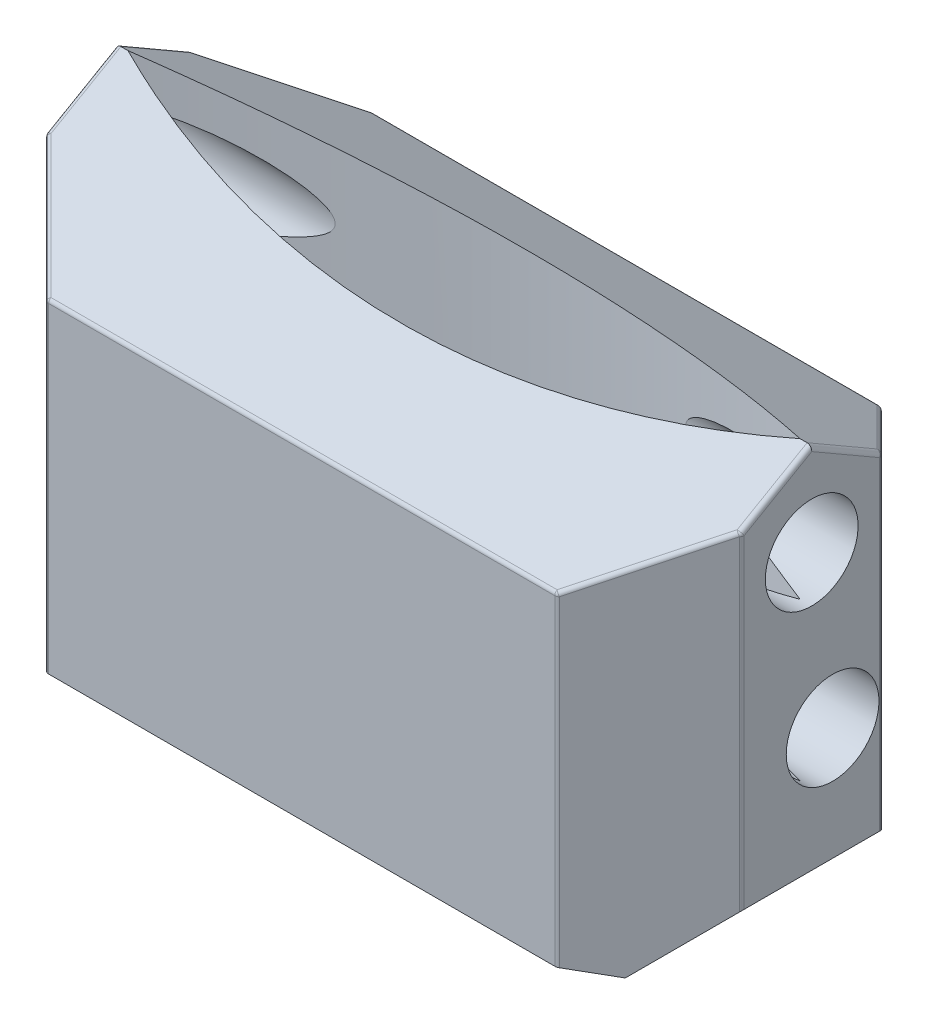
SolidWorks part; units mm, degrees
ref_plane "Front" through (0, 0, 0) normal (0, 0, 1) x (1, 0, 0)
ref_plane "Top" through (0, 0, 0) normal (0, 1, 0) x (1, 0, 0)
ref_plane "Right" through (0, 0, 0) normal (1, 0, 0) x (0, 0, -1)
sketch "Sketch1" plane through (0, 0, 0) normal (0, 1, 0) x (1, 0, 0)
  line L0 (-7.5, 0) -> (7.5, 0) construction
  line L1 (-7.5, 0) -> (-7.5, 1.5)
  line L2 (-7.5, 1.5) -> (-5.5, 3.5)
  line L3 (-5.5, 3.5) -> (5.5, 3.5)
  line L4 (5.5, 3.5) -> (7.5, 1.5)
  line L5 (7.5, 1.5) -> (7.5, 0)
  line L6 (-7.5, 0) -> (-7.25, 0)
  line L7 (7.5, 0) -> (7.25, 0)
  arc A1 (7.25, 0) -> (-7.25, 0) centre (0, -18.6397) ccw
  dimension "D6" = 20
  dimension "D1" = 15
  dimension "D2" = 0.25
  dimension "D3" = 135
  dimension "D4" = 1.5
  dimension "D5" = 2
extrude "Boss-Extrude1" add sketch "Sketch1" along normal mid plane 9
ref_plane "Plane1" through (0, 4.8905, -2.8236) normal (0, -0.866, 0.5) x (-1, 0, 0)
sketch "Sketch2" plane through (0, 4.8905, -2.8236) normal (0, -0.866, 0.5) x (-1, 0, 0)
  line L1 (11.1392, 7.5613) -> (-12.724, 7.5613)
  line L2 (11.1392, 7.5613) -> (11.1392, -13.5041)
  line L3 (11.1392, -13.5041) -> (-12.724, -13.5041)
  line L4 (-12.724, 7.5613) -> (-12.724, -13.5041)
extrude "Cut-Extrude1" cut sketch "Sketch2" along normal up to vertex (1.75 mm away) up to point (-7.5, 4.5, 0)
draft "Draft1" type of draft neutral plane draft angle 15 faces to draft 1 face at (0, -4.5, -1.42) neutral plane through (-5.5, 4.5, -3.5) neutral plane normal (0, 0, -1) parameters "D1"=15
mirror "Mirror2" about plane through (0, 0, 0) normal (0, 0, 1) of bodies 102
combine bodies "Combine2" operation type add bodies to combine 102 103
sketch "Sketch5" plane through (-7.5, 0, 0) normal (-1, 0, 0) x (0, 0, 1)
  circle A0 centre (-0.45, -1) radius 1
  circle A1 centre (0, 2.5) radius 1
  dimension "D1" = 2
  dimension "D2" = 2
  dimension "D3" = 2.5
  dimension "D4" = 1
  dimension "D5" = 0.45
extrude "Cut-Extrude2" cut sketch "Sketch5" against normal through all
fillet "Fillet1" radius 0.1 2 edges at (-7.5, -0.701, -1.5) (7.5, -0.701, -1.5)
fillet "Fillet2" radius 0.1 2 edges at (5.5, -1.0104, -3.5) (-5.5, -1.0104, -3.5)
fillet "Fillet3" radius 0.1 2 edges at (7.5, -0.701, 1.5) (-7.5, -0.701, 1.5)
fillet "Fillet4" radius 0.1 2 edges at (-5.5, -1.0104, 3.5) (5.5, -1.0104, 3.5)
fillet "Fillet5" radius 0.1 18 edges at (7.5, 4.0789, 0.7293) (7.4924, 3.6358, 1.4968) (6.5, 3.0566, 2.5) (5.4968, 2.4837, 3.4924) (-7.5, 4.0789, 0.7293) (-7.4924, 3.6358, 1.4968) (-6.5, 3.0566, 2.5) (-5.4968, 2.4837, 3.4924) (7.5, 4.0789, -0.7293) (7.4924, 3.6358, -1.4968) (6.5, 3.0566, -2.5) (5.4968, 2.4837, -3.4924) (-7.5, 4.0789, -0.7293) (-7.4924, 3.6358, -1.4968) (-6.5, 3.0566, -2.5) (-5.4968, 2.4837, -3.4924) (0, 2.4793, 3.5) (0, 2.4793, -3.5)
sketch "Sketch6" plane through (0, 0, 3.5) normal (0, 0, 1) x (1, 0, 0)
  line L0 (-7.5, -3.4378) -> (-5.5, -5.4378)
  line L4 (-5.5, -5.4378) -> (-7.5, -5.4378)
  line L5 (-7.5, -5.4378) -> (-7.5, -3.4378)
  line L6 (-7.5, -5.047) -> (-7.5, 3.5424) construction
  line L7 (0, 0) -> (0, -1.1315) construction
  line L8 (7.5, -5.4378) -> (7.5, -3.4378)
  line L9 (5.5, -5.4378) -> (7.5, -5.4378)
  line L10 (7.5, -3.4378) -> (5.5, -5.4378)
  dimension "D1" = 2
  dimension "D2" = 2
extrude "Cut-Extrude3" cut sketch "Sketch6" against normal through all both and the other way through all
